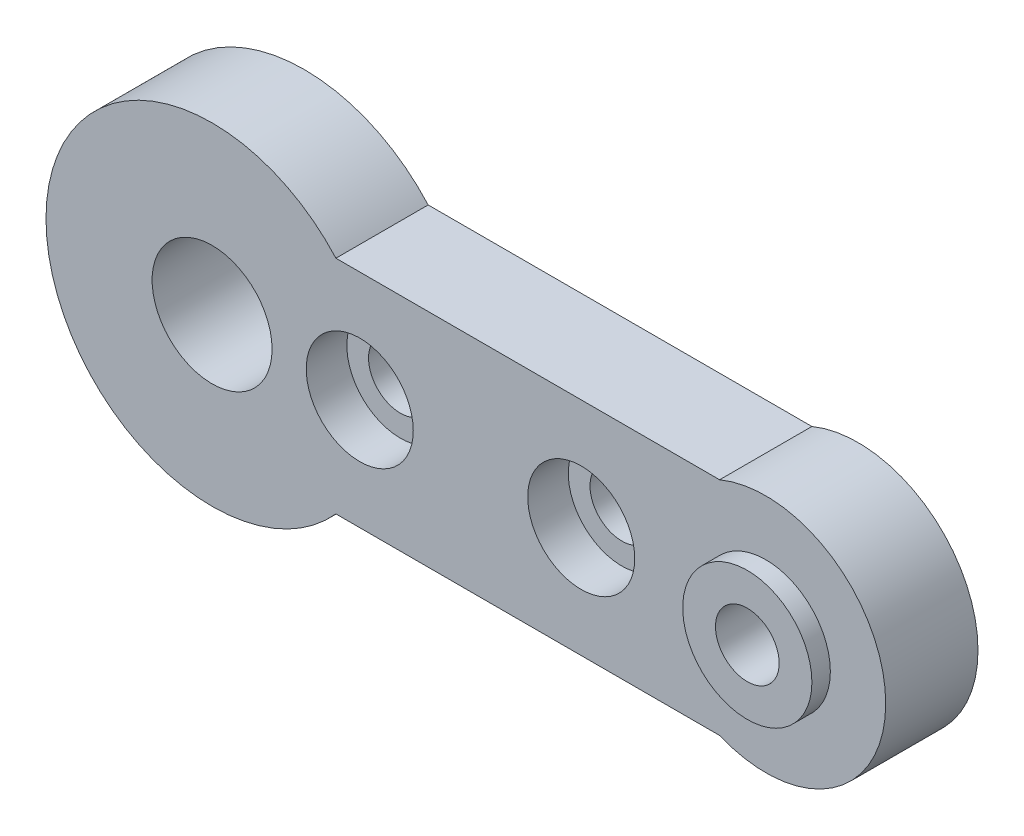
SolidWorks part; units mm, degrees
ref_plane "Front Plane" through (0, 0, 0) normal (0, 0, 1) x (1, 0, 0)
ref_plane "Top Plane" through (0, 0, 0) normal (0, 1, 0) x (1, 0, 0)
ref_plane "Right Plane" through (0, 0, 0) normal (1, 0, 0) x (0, 0, -1)
sketch "Sketch1" plane through (0, 0, 0) normal (0, 0, 1) x (1, 0, 0)
  line L0 (0, -6) -> (30, -6)
  line L1 (30, -6) -> (30, 6)
  line L2 (30, 6) -> (0, 6)
  line L3 (0, 6) -> (0, -6)
extrude "Boss-Extrude1" add sketch "Sketch1" along normal blind 5 from offset 9 offset against normal yes
sketch "Sketch2" plane through (0, 0, 0) normal (0, 0, 1) x (1, 0, 0)
  circle A0 centre (0, 0) radius 9
extrude "Boss-Extrude2" add sketch "Sketch2" along normal blind 5 from offset 9 offset against normal yes
sketch "Sketch3" plane through (0, 0, 0) normal (0, 0, 1) x (1, 0, 0)
  circle A0 centre (30, 0) radius 6.5
extrude "Boss-Extrude3" add sketch "Sketch3" along normal blind 5 from offset 9 offset against normal yes
sketch "Sketch4" plane through (0, 0, 0) normal (0, 0, 1) x (1, 0, 0)
  circle A0 centre (0, 0) radius 3.25
extrude "Cut-Extrude1" cut sketch "Sketch4" against normal through all and the other way through all
sketch "Sketch5" plane through (0, 0, 0) normal (0, 0, 1) x (1, 0, 0)
  circle A0 centre (8, 0) radius 1.725
  circle A1 centre (20, 0) radius 1.725
  circle A2 centre (30, 0) radius 1.725
extrude "Cut-Extrude2" cut sketch "Sketch5" against normal through all and the other way through all
sketch "Sketch6" plane through (0, 0, 0) normal (0, 0, 1) x (1, 0, 0)
  circle A0 centre (8, 0) radius 2.9
extrude "Cut-Extrude3" cut sketch "Sketch6" along normal blind 2.2 from offset 6.2 offset against normal yes
sketch "Sketch7" plane through (0, 0, 0) normal (0, 0, 1) x (1, 0, 0)
  circle A0 centre (20, 0) radius 2.9
extrude "Cut-Extrude4" cut sketch "Sketch7" along normal blind 2.2 from offset 6.2 offset against normal yes
sketch "Sketch8" plane through (0, 0, 0) normal (0, 0, 1) x (1, 0, 0)
  circle A0 centre (30, 0) radius 2.9
extrude "Cut-Extrude5" cut sketch "Sketch8" along normal blind 2.2 from offset 9 offset against normal yes
sketch "Sketch9" plane through (0, 0, 0) normal (0, 0, 1) x (1, 0, 0)
  circle A0 centre (30, 0) radius 3.5
extrude "Boss-Extrude4" add sketch "Sketch9" along normal blind 1 from offset 4 offset against normal yes
sketch "Sketch10" plane through (0, 0, 0) normal (0, 0, 1) x (1, 0, 0)
  circle A0 centre (30, 0) radius 1.725
extrude "Cut-Extrude6" cut sketch "Sketch10" against normal through all and the other way through all
